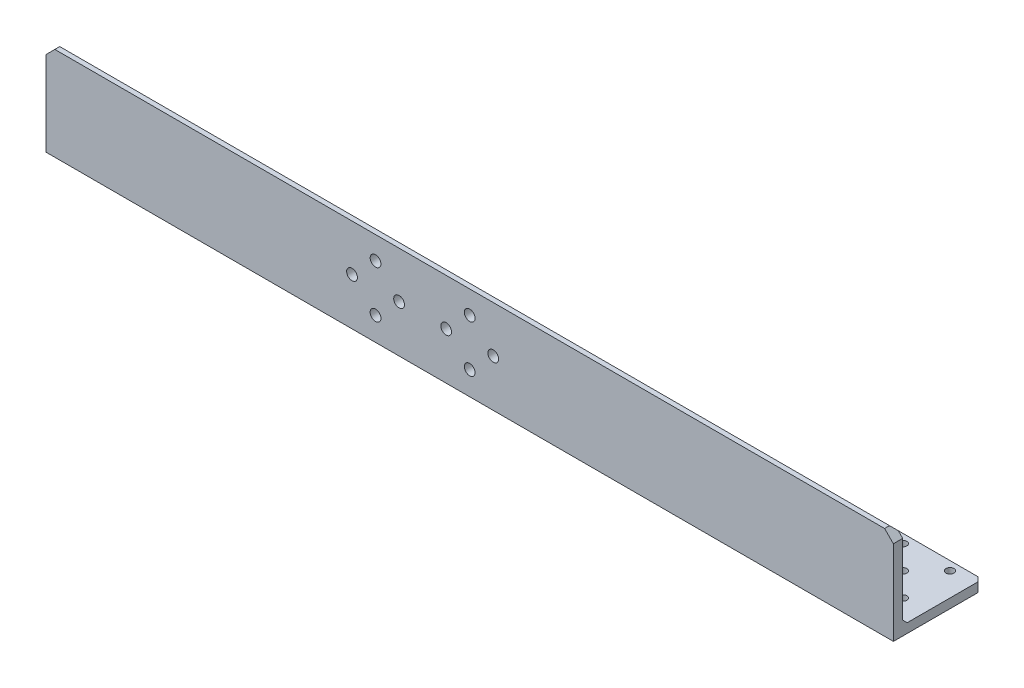
SolidWorks part; units mm, degrees
material "6061-T6 (SS)"
ref_plane "Front" through (0, 0, 0) normal (0, 0, 1) x (1, 0, 0)
ref_plane "Top" through (0, 0, 0) normal (0, 1, 0) x (1, 0, 0)
ref_plane "Right" through (0, 0, 0) normal (1, 0, 0) x (0, 0, -1)
ref_axis "side-side" through (80.9, 0, 0) along (-1, 0, 0)
ref_axis "up-down" through (0, 50, 0) along (0, -1, 0)
ref_axis "front-back" through (0, 0, -80.9) along (0, 0, 1)
sketch3d "3DSketch1"
  circle A8 centre (-128, 0, -19.221) radius 1.85
  circle A9 centre (-128, 0, -27.221) radius 4
  circle A10 centre (-120, 0, -27.221) radius 1.85
  circle A11 centre (-136, 0, -27.221) radius 1.85
  circle A12 centre (-128, 0, -11.221) radius 4
  circle A13 centre (-133.6569, 0, -0.8779) radius 1.85
  circle A14 centre (-122.3431, 0, -0.8779) radius 1.85
  circle A15 centre (-128, 0, -3.221) radius 1.85
  circle A24 centre (-32, 8, 0) radius 1.3525
  arc A25 (-41.208, 16.6084, 0) -> (-41.208, 15.3916, 0) centre (-40, 16, 0) ccw
  circle A26 centre (-32, 24, 0) radius 1.3525
  arc A27 (-25.208, 16.6084, 0.2) -> (-25.208, 15.3916, 0.2) centre (-24, 16, 0.2) ccw
  circle A28 centre (8, 16, 0) radius 1.3525
  arc A29 (-1.208, 8.6084, 0) -> (-1.208, 7.3916, 0) centre (0, 8, 0) ccw
  circle A30 centre (-8, 16, 0.2) radius 1.3525
  arc A31 (-1.208, 24.6084, 0) -> (-1.208, 23.3916, 0) centre (0, 24, 0) ccw
  point P25 (-128, 1.85, -19.221)
  point P27 (-128, 4, -27.221)
  point P29 (-120, 1.85, -27.221)
  point P31 (-136, 1.85, -27.221)
  point P33 (-128, 4, -11.221)
  point P35 (-133.6569, 1.85, -0.8779)
  point P37 (-122.3431, 1.85, -0.8779)
  point P39 (-128, 1.85, -3.221)
  point P69 (-32, 8, -1.3525)
  point P70 (-40, 16, -1.3525)
  point P72 (-32, 24, -1.3525)
  point P73 (-24, 16, -1.1525)
  point P75 (8, 16, -1.3525)
  point P76 (0, 8, -1.3525)
  point P78 (-8, 16, -1.1525)
  point P79 (0, 24, -1.3525)
sketch "Sketch1" plane through (0, 0, 0) normal (1, 0, 0) x (0, 0, -1)
  line L1 (0, 0) -> (31.75, 0)
  line L2 (0, 0) -> (0, 31.75)
  line L3 (0, 31.75) -> (3.175, 31.75)
  line L4 (31.75, 0) -> (31.75, 3.175)
  line L7 (31.75, 3.175) -> (3.175, 3.175)
  line L8 (3.175, 31.75) -> (3.175, 3.175)
  point P1 (3.175, 17.4625)
  dimension "D1" = 3.175
  dimension "D2" = 31.75
extrude "Boss-Extrude1" add sketch "Sketch1" along normal mid plane 288
chamfer "Chamfer1" distance 1.5 angle 45 3 edges at (0, 3.175, -31.75) (0, 3.175, -3.175) (0, 31.75, -3.175)
chamfer "Chamfer2" distance 3 angle 45 4 edges at (-144, 31.75, -0.8375) (-144, 0.8375, -31.75) (144, 0.8375, -31.75) (144, 31.75, -0.8375)
hole_wizard "#6-32 Tapped Hole1" positions "Sketch3" profile "Sketch4" tap size "#6-32" standard "ANSI Inch" end condition through all
sketch "Sketch3" plane through (0, 3.175, 0) normal (0, 1, 0) x (1, 0, 0)
  line L0 (0, 0) -> (0, 68.5449) construction
  point P0 (-136, 27.221)
  point P3 (-120, 27.221)
  point P6 (-128, 19.221)
  point P9 (-136, 11.221)
  point P11 (-120, 11.221)
  point P13 (120, 27.221)
  point P15 (136, 27.221)
  point P17 (128, 19.221)
  point P19 (120, 11.221)
  point P21 (136, 11.221)
  dimension "D1" = 16
  dimension "D2" = 256
sketch "Sketch4" plane through (-136, 3.175, -27.221) normal (1, 0, 0) x (0, 0, 1)
  line L0 (0, 0) -> (0, 3.175)
  line L1 (0, 3.175) -> (1.3525, 3.175)
  line L2 (1.3525, 3.175) -> (1.3525, 0)
  line L5 (1.3525, 0) -> (0, 0)
  line L11 (0, -6.35) -> (0, 107.95) construction
  dimension "Thread Major Dia." = 2.7051
  dimension "Thru Tap Drill Depth" = 3.175
hole_wizard "#6 Clearance Hole1" positions "Sketch5" profile "Sketch6" hole size "#6" standard "ANSI Inch" end condition through all
sketch "Sketch5" plane through (0, 0, -3.175) normal (0, 0, -1) x (-1, 0, 0)
  point P0 (0, 24)
  point P3 (-8, 16)
  point P6 (8, 16)
  point P9 (0, 8)
  point P12 (24, 16)
  point P15 (32, 24)
  point P18 (40, 16)
  point P21 (32, 8)
sketch "Sketch6" plane through (0, 24, -3.175) normal (1, 0, 0) x (0, 1, 0)
  line L0 (0, 0) -> (0, 3.175)
  line L1 (0, 3.175) -> (1.8288, 3.175)
  line L2 (1.8288, 3.175) -> (1.8288, 0)
  line L5 (1.8288, 0) -> (0, 0)
  line L11 (0, -6.35) -> (0, 107.95) construction
  dimension "Thru Hole Dia." = 3.6576
  dimension "Thru Hole Depth" = 3.175
